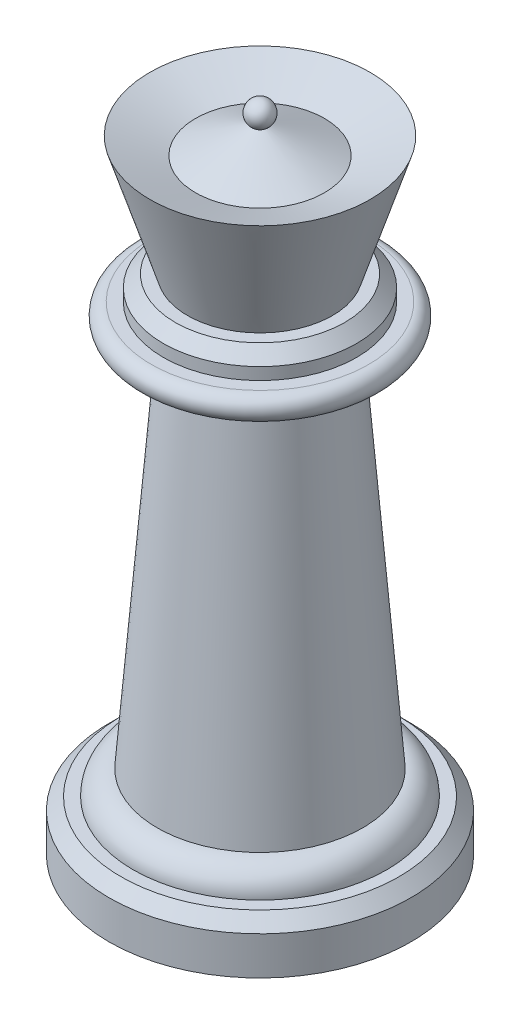
SolidWorks part; units mm, degrees
ref_plane "Front Plane" through (0, 0, 0) normal (0, 0, 1) x (1, 0, 0)
ref_plane "Top Plane" through (0, 0, 0) normal (0, 1, 0) x (1, 0, 0)
ref_plane "Right Plane" through (0, 0, 0) normal (1, 0, 0) x (0, 0, -1)
sketch "Sketch2" plane through (0, 0, 0) normal (0, 0, 1) x (1, 0, 0)
  line L0 (0, 0) -> (0, 41.275)
  line L1 (0, 0) -> (-9.525, 0)
  line L2 (-9.525, 0) -> (-9.525, 3.175)
  line L3 (-9.525, 3.175) -> (-8.001, 3.175)
  line L4 (-8.001, 3.175) -> (-8.001, 4.699)
  line L5 (-8.001, 4.699) -> (-6.477, 4.699)
  line L6 (-6.477, 4.699) -> (-4.572, 28.6766)
  line L7 (-4.572, 28.6766) -> (-6.858, 28.6766)
  line L8 (-7.62, 29.4386) -> (-7.62, 30.2006) construction
  line L9 (-6.858, 30.2006) -> (-6.096, 30.2006)
  line L10 (-6.096, 30.2006) -> (-6.096, 31.7246)
  line L11 (-6.096, 31.7246) -> (-4.572, 31.7246)
  line L12 (-4.572, 31.7246) -> (-6.9468, 39.2544)
  line L13 (-6.9468, 39.2544) -> (-4.064, 38.179)
  line L14 (-4.064, 38.179) -> (-0.3789, 39.8519)
  line L15 (-0.3789, 39.8519) -> (0, 40.0239) construction
  line L16 (-7.62, 28.6766) -> (-7.62, 29.4386) construction
  line L17 (-6.858, 28.6766) -> (-7.62, 28.6766) construction
  line L18 (-7.62, 30.2006) -> (-6.858, 30.2006) construction
  arc A0 (0, 41.275) -> (-0.3789, 39.8519) centre (0, 40.513) ccw
  arc A1 (-0.3789, 39.8519) -> (0, 39.751) centre (0, 40.513) ccw construction
  arc A2 (0, 39.751) -> (0, 41.275) centre (0, 40.513) ccw construction
  arc A3 (-6.858, 30.2006) -> (-6.858, 28.6766) centre (-6.858, 29.4386) ccw
  dimension "D14" = 1.524
  dimension "D1" = 41.275
  dimension "D2" = 9.525
  dimension "D3" = 3.175
  dimension "D4" = 1.524
  dimension "D5" = 1.524
  dimension "D6" = 1.524
  dimension "D7" = 1.524
  dimension "D8" = 28.6766
  dimension "D9" = 1.524
  dimension "D10" = 1.524
  dimension "D12" = 7.62
  dimension "D13" = 1.524
revolve "Revolve1" add sketch "Sketch2" angle 360 about L0
fillet "Fillet1" radius 1.524 1 edges at (0, 4.699, -8.001)
chamfer "Chamfer1" distance 0.762 angle 45 1 edges at (0, 3.175, -9.525)
chamfer "Chamfer2" distance 0.762 angle 45 1 edges at (0, 31.7246, -6.096)
